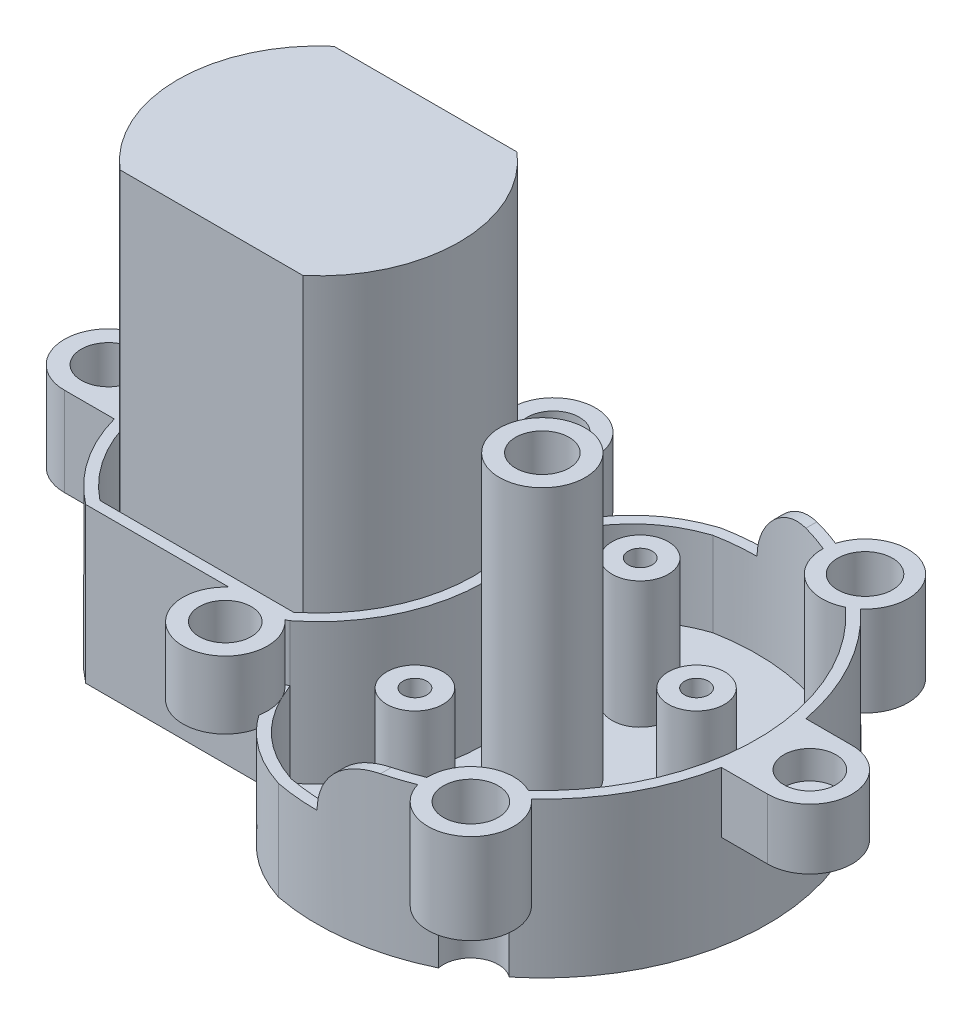
SolidWorks part; units mm, degrees
ref_plane "Plano frontal" through (0, 0, 0) normal (0, 0, 1) x (1, 0, 0)
ref_plane "Plano superior" through (0, 0, 0) normal (0, 1, 0) x (1, 0, 0)
ref_plane "Plano direito" through (0, 0, 0) normal (1, 0, 0) x (0, 0, -1)
sketch "Esboço1" plane through (0, 0, 0) normal (0, 1, 0) x (1, 0, 0)
  line L0 (3.05, 0) -> (-15.9, 0) construction
  line L1 (-15.9, 0) -> (-15.9, -7.65) construction
  line L2 (-9.3823, 7.65) -> (-15.9, 7.65)
  line L3 (-15.9, 7.65) -> (-22.4177, 7.65)
  line L4 (-15.9, 0) -> (-15.9, 7.65) construction
  line L5 (-9.3823, -7.65) -> (-15.9, -7.65)
  line L6 (-15.9, -7.65) -> (-22.4177, -7.65)
  line L7 (-3.05, 0) -> (-3.05, -15.7066) construction
  line L8 (-3.05, 0) -> (-3.05, 15.7066) construction
  line L9 (-9.3823, 9.4) -> (-15.9, 9.4)
  line L10 (-15.9, 9.4) -> (-23.033, 9.4)
  line L11 (-15.9, -9.4) -> (-23.033, -9.4)
  line L12 (-9.3823, -9.4) -> (-15.9, -9.4)
  arc A0 (-15.9, 1.7861) -> (-15.9, -1.7861) centre (0, 0) ccw
  circle A1 centre (0, 0) radius 3.05
  arc A2 (-22.4177, -7.65) -> (-22.4177, 7.65) centre (-15.9, 0) cw
  arc A3 (-9.3823, 7.65) -> (-9.3823, -7.65) centre (-15.9, 0) cw
  arc A4 (-23.033, -9.4) -> (-23.033, 9.4) centre (-15.9, 0) cw
  arc A5 (-3.05, -15.7066) -> (-3.05, 15.7066) centre (0, 0) ccw
  spline S0 degree 2 poles (-3.05, 15.7066) (-7.6546, 14.1972) (-9.3823, 9.4) knots 0 0 0 1 1 1
  spline S1 degree 2 poles (-3.05, -15.7066) (-7.6546, -14.1972) (-9.3823, -9.4) knots 0 0 0 1 1 1
  dimension "D1" = 32
  dimension "D2" = 6.1
  dimension "D5" = 15.3
  dimension "D9" = 10.05
  dimension "D6" = 10.05
  dimension "D10" = 3
  dimension "D3" = 18.95
  dimension "D4" = 7.65
  dimension "D7" = 7.65
  dimension "D8" = 15.3
  dimension "D11" = 4.75
  dimension "D12" = 3
  dimension "D13" = 4.75
  dimension "D14" = 1.75
extrude "Ressalto-extrusão1" add sketch "Esboço1" along normal blind 1 contours S1 A5 S0 L9 L10 A4 L11 L12 A1 L2 A3 L5 L6 A2 L3 | A3 L2 L3 A2 L6 L5 | A1 region at (-15.9, 0, 0) region at (-6.5975, 0, -12.9471) region at (0, 0, 0)
sketch "Esboço2" plane through (0, 1, 0) normal (0, 1, 0) x (1, 0, 0)
  line L0 (-2.8607, 14.9793) -> (-3.0014, 15.716)
  line L1 (-2.8607, -14.9793) -> (-3.0014, -15.716)
  line L3 (-9.3823, 8.65) -> (-23.033, 8.65)
  line L4 (-9.024, 8.65) -> (-22.776, 8.65)
  line L6 (-9.3823, -8.65) -> (-23.033, -8.65)
  line L7 (-9.024, -8.65) -> (-22.776, -8.65)
  arc A0 (-9.024, 8.65) -> (-9.024, -8.65) centre (-15.9, 0) cw
  arc A1 (-9.2513, 9.7486) -> (-9.2513, -9.7486) centre (-15.9, 0) cw
  arc A3 (-3.05, -15.7066) -> (-3.05, 15.7066) centre (0, 0) ccw construction
  arc A4 (-22.5797, 8.8025) -> (-22.5797, -8.8025) centre (-15.9, 0) ccw
  arc A5 (-22.776, 8.65) -> (-22.776, -8.65) centre (-15.9, 0) ccw
  arc A6 (-9.6739, 9.129) -> (-9.6739, -9.129) centre (-15.9, 0) cw construction
  arc A7 (-2.907, -14.9704) -> (-2.907, 14.9704) centre (0, 0) ccw
  arc A8 (-2.8607, -14.9793) -> (-2.8607, 14.9793) centre (0, 0) ccw
  parabola Q9 (-3.05, 15.7066) -> (-9.3823, 9.4) focus (-3.508, 10.3516) apex (-6.5052, 13.7769) construction
  parabola Q23 (-3.05, -15.7066) -> (-9.3823, -9.4) focus (-3.508, -10.3516) apex (-6.5052, -13.7769) construction
  spline S0 degree 3 poles (6928.4434, 818.7063) (671.7103, 559.7976) (43.7684, -62.8146) (-56.8707, 37.4157) (466.501, 784.6442) (1801.6192, 6748.2542) knots -25.390493 -25.390493 -25.390493 -25.390493 0.5 0.5 26.540114 26.540114 26.540114 26.540114 only from (-2.8164, -14.9939) to (-8.6767, -9.1459)
  spline S1 degree 3 poles (-2.8607, -14.9793) (-4.2771, -14.5083) (-5.4472, -13.799) (-7.3442, -11.9096) (-8.084, -10.7346) (-8.6239, -9.2897) knots 0.005157 0.005157 0.005157 0.005157 0.5 0.5 0.984036 0.984036 0.984036 0.984036
  spline S2 degree 3 poles (6928.4434, -818.7063) (671.7103, -559.7976) (43.7684, 62.8146) (-56.8707, -37.4157) (466.501, -784.6442) (1801.6193, -6748.2542) knots -25.390493 -25.390493 -25.390493 -25.390493 0.5 0.5 26.540114 26.540114 26.540114 26.540114 only from (-2.8164, 14.9939) to (-8.6767, 9.1459)
  spline S3 degree 3 poles (-2.8607, 14.9793) (-4.2771, 14.5083) (-5.4472, 13.799) (-7.3442, 11.9096) (-8.084, 10.7346) (-8.6239, 9.2897) knots 0.005157 0.005157 0.005157 0.005157 0.5 0.5 0.984036 0.984036 0.984036 0.984036
  spline M7 degree 2 poles (-9.3823, -9.4) (-7.6546, -14.1972) (-3.05, -15.7066) knots 0 0 0 1 1 1
  arc M8 (-3.05, -15.7066) -> (-3.05, 15.7066) centre (0, 0) ccw
  spline M9 degree 2 poles (-3.05, 15.7066) (-7.6546, 14.1972) (-9.3823, 9.4) knots 0 0 0 1 1 1
  line M10 (-9.3823, 9.4) -> (-23.033, 9.4)
  arc M11 (-23.033, 9.4) -> (-23.033, -9.4) centre (-15.9, 0) ccw
  line M12 (-23.033, -9.4) -> (-9.3823, -9.4)
  dimension "D1" = 0.75
  dimension "D8" = 11.8
  dimension "D2" = 0.75
  dimension "D3" = 0.75
  dimension "D4" = 0.75
  dimension "D5" = 0.75
  dimension "D6" = 0.75
  dimension "D7" = 0.75
extrude "Ressalto-extrusão2" add sketch "Esboço2" along normal blind 10 contours A1 A5 L4 A0 L7 M9 M10 M11 M12 M7 | A8 L1 L0 M8 | S3 L0 A1 M8 M9 | L1 S1 A1 M7 M8 region at (-6.3904, 1, -12.9122) region at (-2.5655, 1, -15.4174) region at (-6.3904, 1, 12.9122) region at (-4.4061, 1, 0)
sketch "Esboço4" plane through (0, 11, 0) normal (0, 1, 0) x (1, 0, 0)
  line L0 (0, 0) -> (0, -15.25) construction
  line L1 (0, -15.25) -> (0, -16)
  line L2 (-9.3823, -9.4) -> (-8.5821, -9.4)
  line L3 (0, 0) -> (0, 15.25) construction
  line L4 (0, 15.25) -> (0, 16)
  line L5 (-9.3823, 9.4) -> (-8.5821, 9.4)
  line L6 (0, 15.25) -> (-8.5821, 9.4)
  line L7 (0, 16) -> (-9.3823, 16)
  line L8 (-9.3823, 16) -> (-9.3823, 9.4)
  line L9 (-9.3823, 9.4) -> (-9.3894, 9.4257)
  line L10 (-8.5821, -9.4) -> (0, -15.25)
  line L11 (0, -16) -> (-9.3823, -16)
  line L12 (-9.3823, -16) -> (-9.3823, -9.4)
  arc A0 (-2.8607, -14.9793) -> (-2.8607, 14.9793) centre (0, 0) ccw construction
  arc A1 (-3.05, -15.7066) -> (-3.05, 15.7066) centre (0, 0) ccw construction
  spline S0 degree 3 poles (-2.8607, -14.9793) (-4.2771, -14.5083) (-5.4472, -13.799) (-7.3442, -11.9096) (-8.084, -10.7346) (-8.6239, -9.2897) knots 0.005157 0.005157 0.005157 0.005157 0.5 0.5 0.984036 0.984036 0.984036 0.984036 construction
  spline S1 degree 3 poles (-2.8607, 14.9793) (-4.2771, 14.5083) (-5.4472, 13.799) (-7.3442, 11.9096) (-8.084, 10.7346) (-8.6239, 9.2897) knots 0.005157 0.005157 0.005157 0.005157 0.5 0.5 0.984036 0.984036 0.984036 0.984036 construction
extrude "Corte-extrusão1" cut sketch "Esboço4" against normal blind 4 contours L11 L12 L2 L10 L1 | L5 L6 L4 L7 L8
fillet "Filete3" radius 4 1 edges at (0, 11, -15.625) type face fillet first side face at (0, 9, -15.625) second side face at (4, 11, 3.8125)
fillet "Filete4" radius 4 1 edges at (0, 11, 15.625) type face fillet first side face at (0, 9, 15.625) second side face at (4.9681, 11, 4.4468)
sketch "Esboço5" plane through (0, 1, 0) normal (0, 1, 0) x (1, 0, 0)
  line L0 (-3.05, 0) -> (-3.05, 10) construction
  line L1 (-3.05, 0) -> (-3.05, -10) construction
  line L2 (-3.05, 10) -> (-1.05, 10) construction
  line L3 (-1.05, 10) -> (-1.05, 8) construction
  line L4 (-3.05, -10) -> (-1.05, -10) construction
  line L5 (-1.05, -10) -> (-1.05, -8) construction
  line L6 (3.05, 0) -> (10.95, 0) construction
  circle A0 centre (0, 0) radius 3.05
  circle A1 centre (0, 0) radius 1.9
  circle A2 centre (-1.05, 8) radius 2
  circle A3 centre (-1.05, -8) radius 2
  circle A4 centre (10.95, 0) radius 2
  dimension "D1" = 6.1
  dimension "D2" = 3.8
  dimension "D7" = 2
  dimension "D10" = 4
  dimension "D3" = 10
  dimension "D4" = 10
  dimension "D5" = 2
  dimension "D6" = 2
  dimension "D8" = 2
  dimension "D9" = 7.9
extrude "Ressalto-extrusão3" add sketch "Esboço5" along normal blind 20
sketch "Esboço9" plane through (0, 21, 0) normal (0, 1, 0) x (1, 0, 0)
  circle A0 centre (-1.05, -8) radius 2.5009
  circle A1 centre (-1.05, 8) radius 2.5198
extrude "Corte-extrusão2" cut sketch "Esboço9" against normal blind 11
sketch "Esboço10" plane through (0, 21, 0) normal (0, 1, 0) x (1, 0, 0)
  circle A0 centre (10.95, 0) radius 2.684
extrude "Corte-extrusão3" cut sketch "Esboço10" against normal blind 9
sketch "Esboço11" plane through (0, 1, 0) normal (0, 1, 0) x (1, 0, 0)
  circle A0 centre (0, 0) radius 1.9
  dimension "D1" = 3.8
extrude "Corte-extrusão4" cut sketch "Esboço11" against normal through all
sketch "Esboço12" plane through (0, 12, 0) normal (0, 1, 0) x (1, 0, 0)
  circle A0 centre (10.95, 0) radius 0.85
  dimension "D1" = 1.7
extrude "Corte-extrusão5" cut sketch "Esboço12" against normal blind 11
sketch "Esboço13" plane through (0, 10, 0) normal (0, 1, 0) x (1, 0, 0)
  circle A0 centre (-1.05, 8) radius 0.85
  circle A1 centre (-1.05, -8) radius 0.85
  dimension "D1" = 1.7
  dimension "D2" = 1.7
extrude "Corte-extrusão6" cut sketch "Esboço13" against normal blind 9
sketch "Esboço14" plane through (0, 11, 0) normal (0, 1, 0) x (1, 0, 0)
  line L2 (0, 0) -> (-30.825, 0) construction
  line L3 (-30.825, 3.125) -> (-27.2787, 3.125)
  line L4 (-30.825, -3.125) -> (-27.2787, -3.125)
  line L7 (-8.5821, 9.4) -> (-23.033, 9.4)
  line L8 (-23.033, -9.4) -> (-8.5821, -9.4)
  arc A2 (-30.825, 3.125) -> (-30.825, -3.125) centre (-30.825, 0) ccw
  arc A3 (-23.033, 9.4) -> (-23.033, -9.4) centre (-15.9, 0) ccw construction
  arc A6 (-8.5821, 9.4) -> (-8.6239, 9.2897) centre (3.1462, 4.8912) ccw
  arc A7 (-23.033, 9.4) -> (-23.033, -9.4) centre (-15.9, 0) ccw
  arc A8 (-8.6239, -9.2897) -> (-8.5821, -9.4) centre (3.0588, -4.9228) ccw
  arc A9 (-8.6239, -9.2897) -> (-8.6239, 9.2897) centre (-15.9, 0) ccw
  arc A11 (-27.2787, 3.125) -> (-27.2787, -3.125) centre (-15.9, 0) ccw
  dimension "D1" = 0
  dimension "D3" = 6.25
extrude "Ressalto-extrusão5" add sketch "Esboço14" against normal blind 6.3
sketch "Esboço16" plane through (0, 11, 0) normal (0, 1, 0) x (1, 0, 0)
  line L0 (-9.024, -8.65) -> (-22.776, -8.65) construction
  line L1 (-9.024, 8.65) -> (-22.776, 8.65) construction
  circle A0 centre (-10.8722, -11.65) radius 3
  circle A1 centre (-10.8722, 11.65) radius 3
  spline S0 degree 3 poles (-8.5821, -9.4) (-8.046, -10.7945) (-7.3202, -11.9335) (-5.4472, -13.799) (-4.2771, -14.5083) (-2.8607, -14.9793) knots 0.005157 0.005157 0.005157 0.005157 0.476819 0.476819 0.971662 0.971662 0.971662 0.971662 construction
  spline S1 degree 3 poles (-2.8607, 14.9793) (-4.2771, 14.5083) (-5.4472, 13.799) (-7.3442, 11.9096) (-8.084, 10.7346) (-8.6239, 9.2897) knots 0.015964 0.015964 0.015964 0.015964 0.510807 0.510807 0.994843 0.994843 0.994843 0.994843 construction
  dimension "D1" = 6
  dimension "D2" = 6
extrude "Ressalto-extrusão6" add sketch "Esboço16" against normal blind 4.8
sketch "Esboço17" plane through (0, 11, 0) normal (0, 1, 0) x (1, 0, 0)
  line L3 (-8.6239, -9.2897) -> (-8.5821, -9.4)
  line L4 (-8.5821, -9.4) -> (-8.8879, -9.4)
  line L5 (-8.6239, 9.2897) -> (-8.5821, 9.4)
  line L6 (-8.5821, 9.4) -> (-8.8879, 9.4)
  spline S0 degree 2 poles (-8.6239, 9.2897) (-8.7415, 9.3772) (-8.8879, 9.4) knots 0 0 0 1 1 1
  spline S1 degree 2 poles (-8.6239, -9.2897) (-8.7415, -9.3772) (-8.8879, -9.4) knots 0 0 0 1 1 1
  dimension "D1" = 0.1
  dimension "D2" = 0.05
  dimension "D3" = 0.1
  dimension "D4" = 0.05
extrude "Corte-extrusão7" cut sketch "Esboço17" against normal blind 4
sketch "Esboço18" plane through (0, 11, 0) normal (0, 1, 0) x (1, 0, 0)
  line L0 (0, 0) -> (19, 0) construction
  line L1 (19, 3) -> (15.7162, 3)
  line L2 (19, -3) -> (15.7162, -3)
  line L3 (15.7162, 3) -> (15.7162, -3)
  arc A0 (19, -3) -> (19, 3) centre (19, 0) ccw
  arc A1 (4, -15.4919) -> (4, 15.4919) centre (0, 0) ccw construction
  dimension "D1" = 6
extrude "Ressalto-extrusão7" add sketch "Esboço18" against normal blind 4.3
sketch "Esboço19" plane through (0, 11, 0) normal (0, 1, 0) x (1, 0, 0)
  circle A0 centre (-10.8722, 11.65) radius 0.9
  circle A1 centre (-10.8722, -11.65) radius 0.9
  dimension "D1" = 1.8
  dimension "D2" = 1.8
extrude "Corte-extrusão8" cut sketch "Esboço19" against normal blind 5
sketch "Esboço20" plane through (0, 11, 0) normal (0, 1, 0) x (1, 0, 0)
  circle A0 centre (19, 0) radius 0.9
  dimension "D1" = 1.8
extrude "Corte-extrusão9" cut sketch "Esboço20" against normal blind 5
sketch "Esboço21" plane through (0, 11, 0) normal (0, 1, 0) x (1, 0, 0)
  circle A0 centre (-30.825, 0) radius 1.925
  dimension "D1" = 3.85
extrude "Corte-extrusão10" cut sketch "Esboço21" against normal blind 7
sketch "Esboço22" plane through (0, 11, 0) normal (0, 1, 0) x (1, 0, 0)
  circle A0 centre (-10.8722, 11.65) radius 1.85
  circle A1 centre (-10.8722, -11.65) radius 1.85
  dimension "D1" = 3.7
  dimension "D2" = 3.7
extrude "Corte-extrusão11" cut sketch "Esboço22" against normal blind 3
sketch "Esboço23" plane through (0, 11, 0) normal (0, 1, 0) x (1, 0, 0)
  circle A0 centre (19, 0) radius 1.85
  dimension "D1" = 3.7
extrude "Corte-extrusão12" cut sketch "Esboço23" against normal blind 2
sketch "Esboço24" plane through (0, 1, 0) normal (0, 1, 0) x (1, 0, 0)
  line L0 (-15.9, 8.65) -> (-15.9, 0) construction
  line L1 (-9.024, 8.65) -> (-22.776, 8.65) construction
  line L2 (-15.9, 0) -> (0, 0) construction
  line L3 (-15.9, 7.6) -> (-22.3992, 7.6)
  line L4 (-15.9, 7.6) -> (-9.4008, 7.6)
  line L5 (-15.9, 0) -> (-15.9, -7.6) construction
  line L6 (-15.9, -7.6) -> (-9.4008, -7.6)
  line L7 (-15.9, -7.6) -> (-22.3992, -7.6)
  arc A0 (-22.3992, 7.6) -> (-22.3992, -7.6) centre (-15.9, 0) ccw
  arc A1 (-9.4008, -7.6) -> (-9.4008, 7.6) centre (-15.9, 0) ccw
  dimension "D3" = 10
  dimension "D4" = 10
  dimension "D1" = 7.6
  dimension "D2" = 7.6
extrude "Ressalto-extrusão8" add sketch "Esboço24" along normal blind 30
sketch "Esboço25" plane through (0, 0, 0) normal (0, -1, 0) x (1, 0, 0)
  circle A0 centre (-15.9, 0) radius 0.9
  dimension "D1" = 1.8
extrude "Ressalto-extrusão9" add sketch "Esboço25" along normal blind 6
sketch "Esboço27" plane through (0, 11, 0) normal (0, 1, 0) x (1, 0, 0)
  line L0 (0, 0) -> (8.921, 13.9991) construction
  line L1 (8.921, 13.9991) -> (19, 0) construction
  line L2 (0, 0) -> (8.921, -13.9991) construction
  line L3 (8.921, -13.9991) -> (19, 0) construction
  circle A0 centre (8.921, 13.9991) radius 3.05
  circle A1 centre (8.921, -13.9991) radius 3.05
  dimension "D5" = 6.1
  dimension "D6" = 6.1
  dimension "D1" = 17.25
  dimension "D2" = 16.6
  dimension "D3" = 16.6
  dimension "D4" = 17.25
extrude "Ressalto-extrusão10" add sketch "Esboço27" against normal blind 11
sketch "Esboço29" plane through (0, 0, 0) normal (0, -1, 0) x (1, 0, 0)
  arc A0 (5.9884, 14.8371) -> (10.9192, 11.6949) centre (0, 0) cw
  arc A1 (10.9192, 11.6949) -> (5.9884, 14.8371) centre (8.921, 13.9991) ccw construction
  arc A2 (10.9192, -11.6949) -> (5.9884, -14.8371) centre (0, 0) cw
  arc A3 (5.9884, -14.8371) -> (10.9192, -11.6949) centre (8.921, -13.9991) ccw construction
  arc A4 (5.9884, 14.8371) -> (10.9192, 11.6949) centre (8.921, 13.9991) cw
  arc A5 (10.9192, -11.6949) -> (5.9884, -14.8371) centre (8.921, -13.9991) cw
  arc M2 (10.9192, 11.6949) -> (5.9884, 14.8371) centre (8.921, 13.9991) ccw
  arc M10 (5.9884, -14.8371) -> (10.9192, -11.6949) centre (8.921, -13.9991) ccw
extrude "Corte-extrusão14" cut sketch "Esboço29" against normal blind 4.6 contours A2 M10 | A0 M2 region at (9.4203, 0, 14.7827) region at (9.4203, 0, -14.7827)
sketch "Esboço30" plane through (0, 11, 0) normal (0, 1, 0) x (1, 0, 0)
  circle A0 centre (8.921, 13.9991) radius 1.95
  circle A1 centre (8.921, -13.9991) radius 1.95
  dimension "D1" = 3.9
  dimension "D2" = 3.9
extrude "Corte-extrusão15" cut sketch "Esboço30" against normal through all
